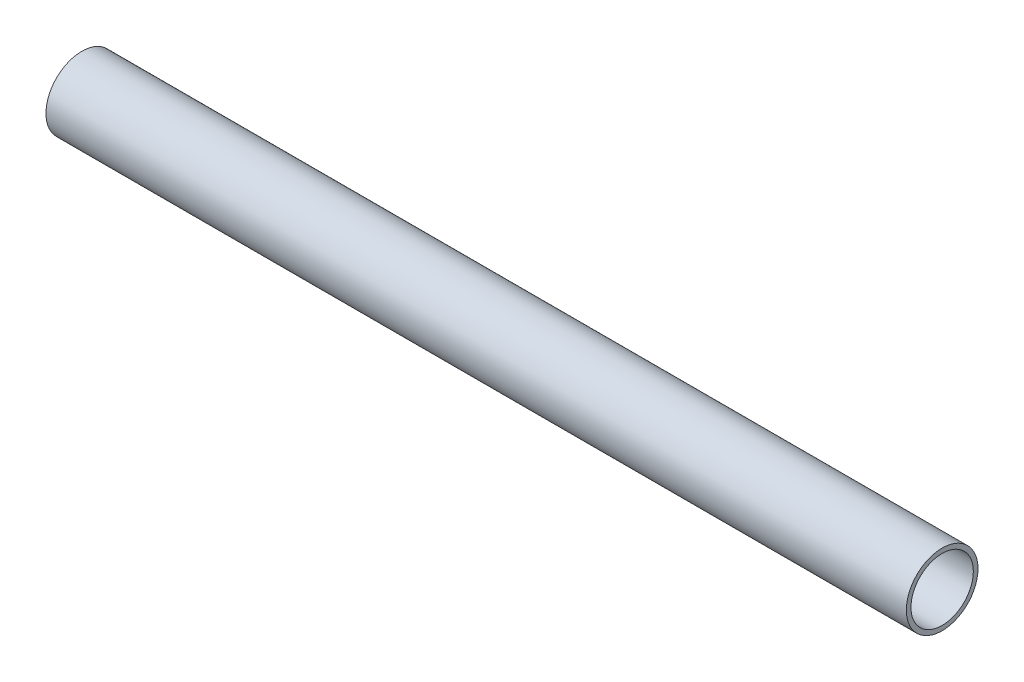
SolidWorks part; units mm, degrees
ref_plane "Front Plane" through (0, 0, 0) normal (0, 0, 1) x (1, 0, 0)
ref_plane "Top Plane" through (0, 0, 0) normal (0, 1, 0) x (1, 0, 0)
ref_plane "Right Plane" through (0, 0, 0) normal (1, 0, 0) x (0, 0, -1)
sketch "Sketch1" plane through (0, 0, 0) normal (1, 0, 0) x (0, 0, -1)
  circle A0 centre (0, 0) radius 11.049
  circle A1 centre (0, 0) radius 12.7
  dimension "D1" = 22.098
  dimension "D2" = 25.4
extrude "Boss-Extrude1" add sketch "Sketch1" along normal blind 152.4 and the other way blind 152.4
